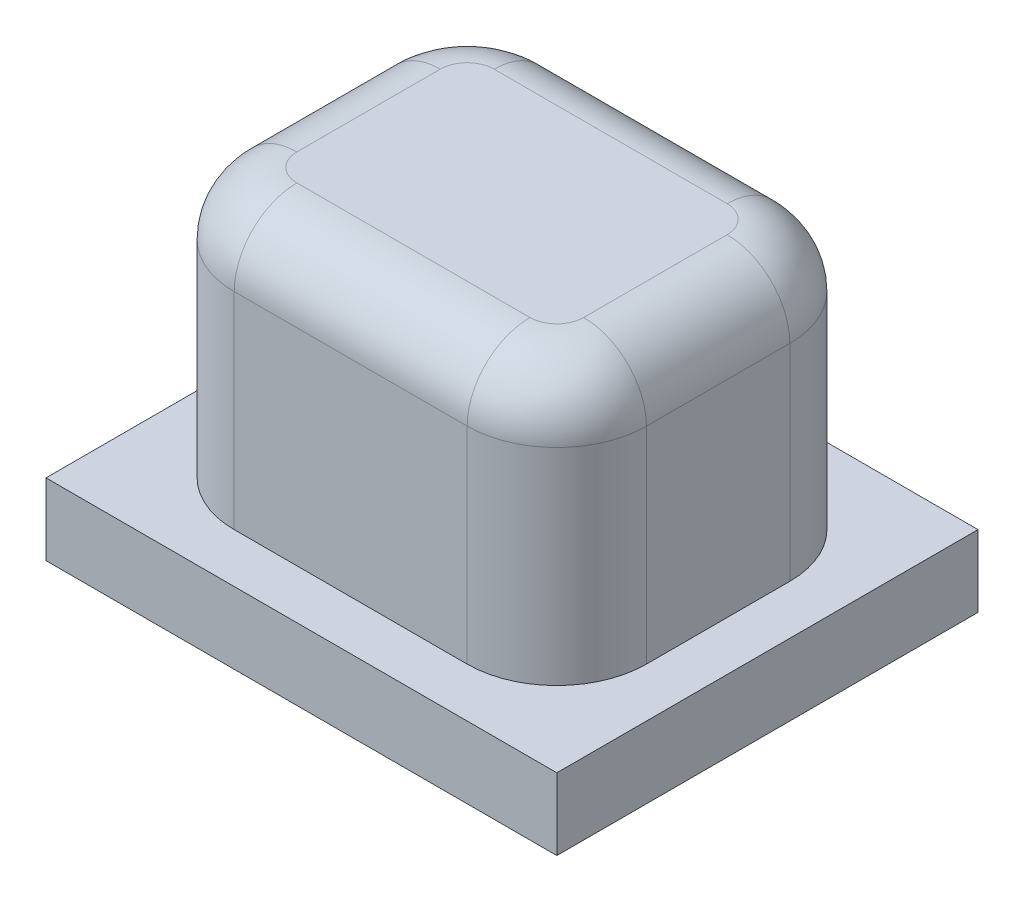
SolidWorks part; units mm, degrees
ref_plane "前视基准面" through (0, 0, 0) normal (0, 0, 1) x (1, 0, 0)
ref_plane "上视基准面" through (0, 0, 0) normal (0, 1, 0) x (1, 0, 0)
ref_plane "右视基准面" through (0, 0, 0) normal (1, 0, 0) x (0, 0, -1)
sketch "草图1" plane through (0, 0, 0) normal (0, 1, 0) x (1, 0, 0)
  line L1 (-1.3, -1.8) -> (1.3, -1.8)
  line L2 (-2.3, -0.8) -> (-2.3, 0.8)
  line L3 (-1.3, 1.8) -> (1.3, 1.8)
  line L4 (2.3, -0.8) -> (2.3, 0.8)
  line L5 (-2.3, -1.8) -> (2.3, 1.8) construction
  line L6 (-2.3, 1.8) -> (2.3, -1.8) construction
  arc A0 (1.3, -1.8) -> (2.3, -0.8) centre (1.3, -0.8) ccw
  arc A1 (-1.3, -1.8) -> (-2.3, -0.8) centre (-1.3, -0.8) cw
  arc A2 (1.3, 1.8) -> (2.3, 0.8) centre (1.3, 0.8) cw
  arc A3 (-2.3, 0.8) -> (-1.3, 1.8) centre (-1.3, 0.8) cw
  point P0 (0, 0)
  dimension "D3" = 1
  dimension "D1" = 4.6
  dimension "D2" = 3.6
extrude "按钮柱体" add sketch "草图1" along normal blind 3
sketch "草图2" plane through (0, 0, 0) normal (0, -1, 0) x (1, 0, 0)
  line L1 (-2.85, -2.35) -> (2.85, -2.35)
  line L2 (-2.85, -2.35) -> (-2.85, 2.35)
  line L3 (-2.85, 2.35) -> (2.85, 2.35)
  line L4 (2.85, -2.35) -> (2.85, 2.35)
  line L5 (-2.85, -2.35) -> (2.85, 2.35) construction
  line L6 (-2.85, 2.35) -> (2.85, -2.35) construction
  point P0 (0, 0)
  dimension "D1" = 5.7
  dimension "D2" = 4.7
extrude "按钮底座" add sketch "草图2" along normal blind 0.8
sketch "草图3" plane through (0, -0.8, 0) normal (0, -1, 0) x (1, 0, 0)
  line L1 (-0.75, -1.25) -> (0.75, -1.25)
  line L2 (-1.75, -0.25) -> (-1.75, 0.25)
  line L3 (-0.75, 1.25) -> (0.75, 1.25)
  line L4 (1.75, -0.25) -> (1.75, 0.25)
  line L5 (-1.75, -1.25) -> (1.75, 1.25) construction
  line L6 (-1.75, 1.25) -> (1.75, -1.25) construction
  arc A1 (0.75, 1.25) -> (1.75, 0.25) centre (0.75, 0.25) cw
  arc A2 (-0.75, -1.25) -> (-1.75, -0.25) centre (-0.75, -0.25) cw
  arc A3 (0.75, -1.25) -> (1.75, -0.25) centre (0.75, -0.25) ccw
  arc A4 (-1.75, 0.25) -> (-0.75, 1.25) centre (-0.75, 0.25) cw
  point P0 (0, 0)
  dimension "D1" = 3.5
  dimension "D3" = 1
  dimension "D2" = 2.5
extrude "底部凹槽" cut sketch "草图3" against normal blind 2.8
fillet "圆角1" radius 0.7 8 edges at (2.0071, 3, -1.5071) (2.3, 3, 0) (2.0071, 3, 1.5071) (0, 3, 1.8) (-2.0071, 3, 1.5071) (-2.3, 3, 0) (-2.0071, 3, -1.5071) (0, 3, -1.8)
